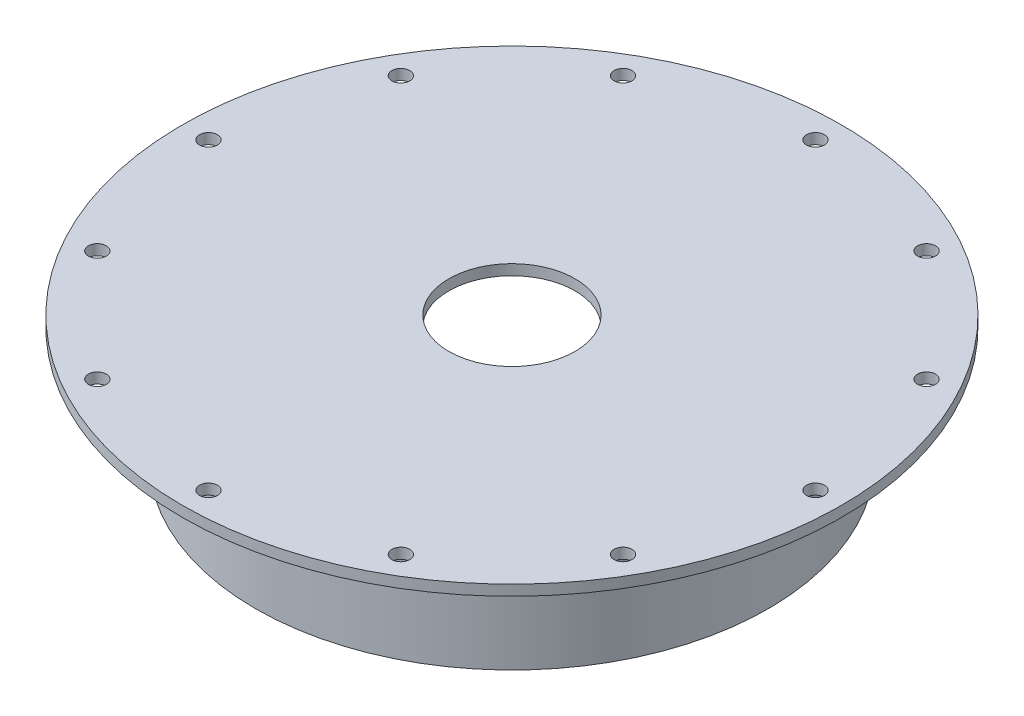
SolidWorks part; units mm, degrees
material "6063-T6"
ref_plane "Front Plane" through (0, 0, 0) normal (0, 0, 1) x (1, 0, 0)
ref_plane "Top Plane" through (0, 0, 0) normal (0, 1, 0) x (1, 0, 0)
ref_plane "Right Plane" through (0, 0, 0) normal (1, 0, 0) x (0, 0, -1)
ref_axis "Axis1" through (0, 55, 0) along (0, -1, 0)
sketch "Sketch1" plane through (0, 0, 0) normal (0, 0, 1) x (1, 0, 0)
  line L0 (-49.784, 0) -> (-38.735, 0)
  line L1 (0, 55) -> (0, -55) construction
  line L2 (-49.784, 0) -> (-49.784, 1.5875)
  line L3 (-49.784, 1.5875) -> (-9.525, 1.5875)
  line L4 (-49.784, 1.5875) -> (-9.525, 1.5875) construction
  line L5 (-9.525, 1.5875) -> (-9.525, 0)
  line L6 (-9.525, 0) -> (0, 0) construction
  line L7 (-49.784, 0) -> (-49.784, 1.5875) construction
  line L8 (-9.525, 1.5875) -> (-9.525, 0) construction
  line L9 (-38.735, 0) -> (-38.735, -17.4625)
  line L10 (-38.735, -17.4625) -> (-35.56, -17.4625)
  line L11 (-35.56, -17.4625) -> (-35.56, -3.175)
  line L12 (-32.385, 0) -> (-9.525, 0)
  line L13 (0, -201000) -> (0, 249000) construction
  arc A0 (-35.56, -3.175) -> (-32.385, 0) centre (-32.385, -3.175) cw
  point P18 (-35.56, 0)
  dimension "D4" = 3.175
  dimension "D1" = 3.175
  dimension "D2" = 38.735
  dimension "D3" = 17.4625
revolve "Revolve1" add sketch "Sketch1" angle 360 about axis through (0, 55, 0) along (0, -1, 0)
ref_plane "Hole Location Plane" through (0, 3.175, 0) normal (0, 1, 0) x (1, 0, 0)
sketch "Hole Location" plane through (0, 3.175, 0) normal (0, 1, 0) x (1, 0, 0)
  line L0 (0, 0) -> (-45.847, 0) construction
  circle A0 centre (0, 0) radius 45.847 construction
  dimension "D1" = 91.694
hole_wizard "#36 (0.1065) Diameter Hole1" positions "Sketch4" profile "Sketch5" hole size "#36" standard "ANSI Inch" end condition through all
sketch "Sketch4" plane through (0, 1.5875, 0) normal (0, 1, 0) x (1, 0, 0)
  point P0 (-45.847, 0)
sketch "Sketch5" plane through (-45.847, 1.5875, 0) normal (1, 0, 0) x (0, 0, 1)
  line L0 (0, 0) -> (0, 19.05)
  line L1 (0, 19.05) -> (1.3525, 19.05)
  line L2 (1.3525, 19.05) -> (1.3525, 0)
  line L5 (1.3525, 0) -> (0, 0)
  line L11 (0, -6.35) -> (0, 107.95) construction
  dimension "Thru Hole Dia." = 2.7051
  dimension "Thru Hole Depth" = 19.05
pattern_circular "CirPattern1" count 12 every 30 about axis through (0, 55, 0) along (0, -1, 0) of "#36 (0.1065) Diameter Hole1"
equation "\"D1@Hole Location\"=\"TANK DIAMETER@Cryo Tank.Assembly\"+\"GASKET SEAT THICKNESS@Cryo Tank.Assembly\"+\"LINER THICKNESS@Cryo Tank.Assembly\"+\"LINER COMPRESSION DELTA@Cryo Tank.Assembly\"+\"SHRINK FIT DELTA@Cryo Tank.Assembly\""
equation "\"D2@Sketch1\"=\"TANK DIAMETER@Cryo Tank.Assembly\"/2+\"LINER COMPRESSION DELTA@Cryo Tank.Assembly\"+\"SHRINK FIT DELTA@Cryo Tank.Assembly\""
equation "\"D3@Sketch1\"=0.5+0.125+0.0625"
